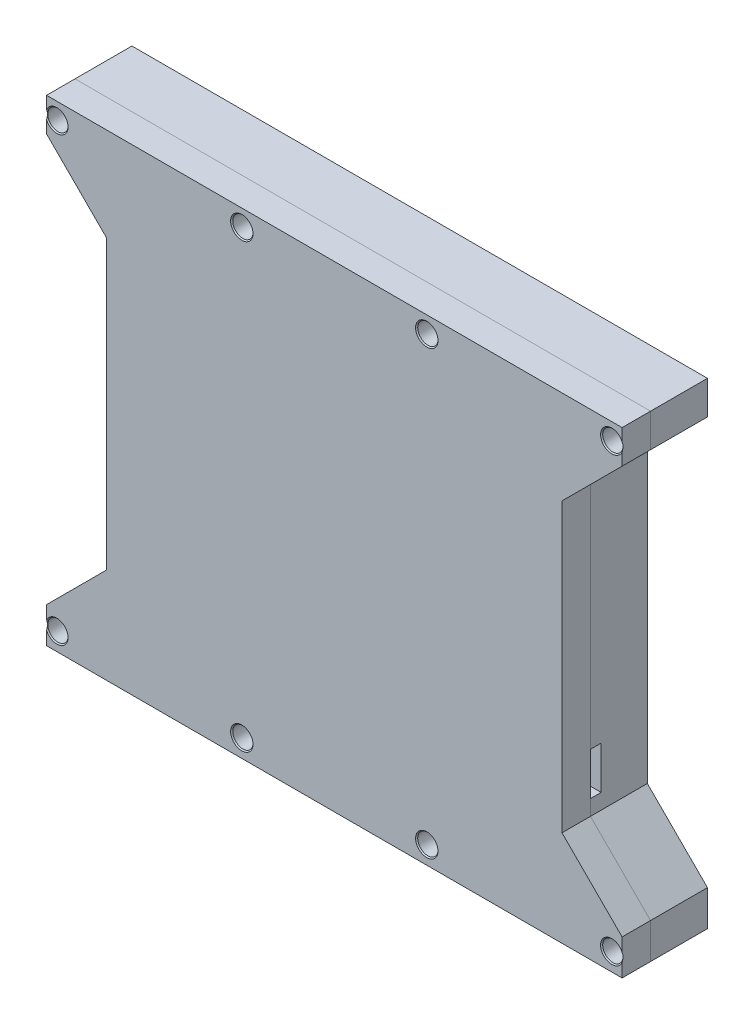
SolidWorks part; units mm, degrees
ref_plane "Front Plane" through (0, 0, 0) normal (0, 0, 1) x (1, 0, 0)
ref_plane "Top Plane" through (0, 0, 0) normal (0, 1, 0) x (1, 0, 0)
ref_plane "Right Plane" through (0, 0, 0) normal (1, 0, 0) x (0, 0, -1)
sketch "Sketch1" plane through (0, 0, 0) normal (0, 0, 1) x (1, 0, 0)
  line L9 (98.5, 67.7634) -> (0, 67.7634) construction
  line L10 (-90.3, -66.2366) -> (0, -66.2366) construction
  line L11 (-80.9, 58.3634) -> (-64, 41.4634)
  line L12 (-64, 41.4634) -> (-64, -39.3366)
  line L13 (-64, -39.3366) -> (-80.9, -56.2366)
  line L18 (-80.9, 67.7634) -> (-80.9, 61.3891) construction
  line L19 (0, -30.5366) -> (0, -67.9366) construction
  line L20 (-80.9, 58.3634) -> (-80.9, 67.7634)
  line L22 (-80.9, -56.2366) -> (-80.9, 58.3634) construction
  line L23 (-80.9, -66.2366) -> (80.9, -66.2366)
  line L25 (-80.9, -66.2366) -> (-80.9, -56.2366)
  line L26 (-80.9, 67.7634) -> (80.9, 67.7634)
  line L27 (80.9, -66.2366) -> (80.9, -56.2366)
  line L28 (0, 58.3634) -> (0, -66.2366) construction
  line L29 (252.3, -56.2366) -> (71.7, -56.2366) construction
  line L30 (-60, -56.2366) -> (60, -56.2366)
  line L31 (-60, -56.2366) -> (-60, 58.3634)
  line L32 (-60, 58.3634) -> (60, 58.3634)
  line L33 (60, -56.2366) -> (60, 58.3634)
  line L34 (69.2, 58.3634) -> (254.8, 58.3634) construction
  line L35 (80.9, -66.2366) -> (80.9, -56.2366)
  line L36 (64, -39.3366) -> (80.9, -56.2366)
  line L37 (64, 41.4634) -> (64, -39.3366)
  line L38 (80.9, 58.3634) -> (64, 41.4634)
  line L39 (80.9, 58.3634) -> (80.9, 67.7634)
  line L40 (80.9, 58.3634) -> (80.9, 67.7634)
  line L41 (80.9, -56.2366) -> (80.9, 58.3634) construction
  line L42 (-92.8, 58.3634) -> (0, 58.3634) construction
  point P37 (0, 67.7634)
  dimension "D1" = 45
  dimension "D2" = 4
  dimension "D3" = 120
  dimension "D4" = 45
  dimension "D5" = 4
extrude "Boss-Extrude1" add sketch "Sketch1" along normal blind 0.8 contours L23 L27 L26 L25 L33 L30 L31 L32 | L30 L33 L32 L31 region at (-78.7992, 63.0634, 0) region at (0, 1.0634, 0)
extrude "Boss-Extrude2" add sketch "Sketch1<3>" along normal blind 24 contours L26 L25 region at (-78.7992, 63.0634, 0)
sketch "Sketch1<3>" plane through (0, 0, 0) normal (0, 0, 1) x (1, 0, 0) same geometry as "Sketch1"
extrude "Boss-Extrude3" add sketch "Sketch1<4>" against normal blind 0.8 from surface contours L38 L39 L26 L20 L11 L12 L13 L25 L23 L27 L36 L37 L33 L30 L31 L32 | L30 L33 L32 L31 region at (-78.7992, 63.0634, 0) region at (0, 1.0634, 0) starting at face at (0, 1.0634, 24)
sketch "Sketch1<4>" plane through (0, 0, 0) normal (0, 0, 1) x (1, 0, 0) same geometry as "Sketch1"
sketch "Sketch2" plane through (0, 0, 0) normal (0, 0, -1) x (-1, 0, 0)
  circle A0 centre (78, -61.2366) radius 1.75
  circle A1 centre (26, -61.2366) radius 1.75
  circle A2 centre (-26, -61.2366) radius 1.75
  circle A3 centre (-78, -61.2366) radius 1.75
  circle A4 centre (78, 63.0634) radius 1.75
  circle A5 centre (26, 63.0634) radius 1.75
  circle A6 centre (-26, 63.0634) radius 1.75
  circle A7 centre (-78, 63.0634) radius 1.75
  circle A8 centre (78, 63.0634) radius 1.75 construction
  circle A9 centre (26, 63.0634) radius 1.75 construction
  circle A10 centre (-26, 63.0634) radius 1.75 construction
  dimension "D1" = 3.5
extrude "Cut-Extrude1" cut sketch "Sketch2" against normal through all
sketch "Sketch3" plane through (0, 0, 24) normal (0, 0, 1) x (1, 0, 0)
  circle A0 centre (-78, -61.2366) radius 2.85
  circle A1 centre (-26, -61.2366) radius 2.85
  circle A2 centre (26, -61.2366) radius 2.85
  circle A3 centre (78, -61.2366) radius 2.85
  circle A4 centre (78, 63.0634) radius 2.85
  circle A5 centre (26, 63.0634) radius 2.85
  circle A6 centre (-26, 63.0634) radius 2.85
  circle A7 centre (-78, 63.0634) radius 2.85
  dimension "D1" = 5.7
extrude "Cut-Extrude2" cut sketch "Sketch3" against normal blind 5.8
ref_plane "Plane1" through (0, 0, 16) normal (0, 0, 1) x (1, 0, 0)
sketch "Sketch4" plane through (0, 0, 0.8) normal (0, 0, 1) x (1, 0, 0)
  line L1 (-50, -46) -> (22, -46)
  line L2 (-50, -46) -> (-50, 46)
  line L3 (-50, 46) -> (22, 46)
  line L4 (22, -46) -> (22, 46)
  line L5 (-60, 58.3634) -> (-60, -56.2366) construction
  line L6 (32, 46) -> (56, 46)
  line L7 (32, 46) -> (32, -8)
  line L8 (32, -8) -> (56, -8)
  line L9 (56, 46) -> (56, -8)
  line L15 (-39, -20.9366) -> (-49, -20.9366) construction
  line L16 (-39, -25.9366) -> (-49, -25.9366)
  line L17 (-39, -15.9366) -> (-49, -15.9366)
  line L18 (-100, -48.9366) -> (-100, 51.0634) construction
  line L19 (-93, -55.9366) -> (93, -55.9366) construction
  circle A0 centre (-44.92, 40.41) radius 1.6
  circle A1 centre (16.03, 40.41) radius 1.6
  circle A2 centre (16.03, -40.92) radius 1.6
  circle A3 centre (-44.92, -40.92) radius 1.6
  circle A4 centre (53.5, 37) radius 1.5
  circle A5 centre (34.8, 2.3) radius 1.5
  arc A6 (-39, -25.9366) -> (-39, -15.9366) centre (-39, -20.9366) ccw
  arc A7 (-49, -15.9366) -> (-49, -25.9366) centre (-49, -20.9366) ccw
  point P21 (22, 0)
  point P30 (-44, -20.9366)
  point P40 (-34, -20.9366)
  dimension "D3" = 3.2
  dimension "D12" = 3
  dimension "D22" = 20
  dimension "D19" = 5
  dimension "D1" = 72
  dimension "D2" = 92
  dimension "D4" = 5.08
  dimension "D5" = 5.59
  dimension "D6" = 5.08
  dimension "D7" = 10
  dimension "D8" = 5.97
  dimension "D9" = 24
  dimension "D10" = 54
  dimension "D11" = 10
  dimension "D13" = 7.5
  dimension "D14" = 1
  dimension "D15" = 8.8
  dimension "D16" = 1.3
  dimension "D17" = 56
  dimension "D18" = 35
sketch "Sketch6" plane through (0, 0, 0.8) normal (0, 0, 1) x (1, 0, 0)
  line L0 (-50, -46) -> (-50, 46) construction
  line L1 (-42.17, 38.8223) -> (-42.17, 41.9977)
  line L2 (-42.17, 41.9977) -> (-44.92, 43.5854)
  line L3 (-44.92, 43.5854) -> (-47.67, 41.9977)
  line L4 (-47.67, 41.9977) -> (-47.67, 38.8223)
  line L5 (-47.67, 38.8223) -> (-44.92, 37.2346)
  line L6 (-44.92, 37.2346) -> (-42.17, 38.8223)
  line L8 (18.78, 38.8223) -> (18.78, 41.9977)
  line L9 (18.78, 41.9977) -> (16.03, 43.5854)
  line L10 (16.03, 43.5854) -> (13.28, 41.9977)
  line L11 (13.28, 41.9977) -> (13.28, 38.8223)
  line L12 (13.28, 38.8223) -> (16.03, 37.2346)
  line L13 (16.03, 37.2346) -> (18.78, 38.8223)
  line L14 (18.78, -42.5077) -> (18.78, -39.3323)
  line L15 (18.78, -39.3323) -> (16.03, -37.7446)
  line L16 (16.03, -37.7446) -> (13.28, -39.3323)
  line L17 (13.28, -39.3323) -> (13.28, -42.5077)
  line L18 (13.28, -42.5077) -> (16.03, -44.0954)
  line L19 (16.03, -44.0954) -> (18.78, -42.5077)
  line L20 (-42.17, -39.3323) -> (-44.92, -37.7446)
  line L21 (-44.92, -37.7446) -> (-47.67, -39.3323)
  line L22 (-47.67, -39.3323) -> (-47.67, -42.5077)
  line L23 (-47.67, -42.5077) -> (-44.92, -44.0954)
  line L24 (-44.92, -44.0954) -> (-42.17, -42.5077)
  line L25 (-42.17, -42.5077) -> (-42.17, -39.3323)
  circle A0 centre (-44.92, 40.41) radius 2.75 construction
  circle A1 centre (-44.92, 40.41) radius 3.95
  circle A2 centre (16.03, 40.41) radius 2.75 construction
  circle A3 centre (16.03, -40.92) radius 2.75 construction
  circle A4 centre (-44.92, -40.92) radius 2.75 construction
  circle A5 centre (-44.92, -40.92) radius 3.95
  circle A6 centre (16.03, -40.92) radius 3.95
  circle A7 centre (16.03, 40.41) radius 3.95
  dimension "D1" = 5.5
  dimension "D2" = 1.2
extrude "Boss-Extrude4" add sketch "Sketch6" along normal blind 4.5
extrude "Boss-Extrude5" add sketch "Sketch6<3>" along normal blind 0.5 contours L5 L6 L1 L2 L3 L4 | L12 L13 L8 L9 L10 L11 | L18 L19 L14 L15 L16 L17 | L24 L25 L20 L21 L22 L23 region at (-44.92, 40.41, 0.8) region at (16.03, 40.41, 0.8) region at (16.03, -40.92, 0.8) region at (-44.92, -40.92, 0.8)
sketch "Sketch6<3>" plane through (0, 0, 0.8) normal (0, 0, 1) x (1, 0, 0) same geometry as "Sketch6"
sketch "Sketch7" plane through (0, 0, 0.8) normal (0, 0, 1) x (1, 0, 0)
  line L0 (16.03, 43.5854) -> (13.28, 41.9977) construction
  line L1 (55.0877, 39.75) -> (51.9123, 39.75)
  line L2 (51.9123, 39.75) -> (50.3246, 37)
  line L3 (50.3246, 37) -> (51.9123, 34.25)
  line L4 (51.9123, 34.25) -> (55.0877, 34.25)
  line L5 (55.0877, 34.25) -> (56.6754, 37)
  line L6 (56.6754, 37) -> (55.0877, 39.75)
  line L7 (36.3877, 5.05) -> (33.2123, 5.05)
  line L8 (33.2123, 5.05) -> (31.6246, 2.3)
  line L9 (31.6246, 2.3) -> (33.2123, -0.45)
  line L10 (33.2123, -0.45) -> (36.3877, -0.45)
  line L11 (36.3877, -0.45) -> (37.9754, 2.3)
  line L12 (37.9754, 2.3) -> (36.3877, 5.05)
  circle A0 centre (53.5, 37) radius 2.75 construction
  circle A1 centre (34.8, 2.3) radius 2.75 construction
  circle A2 centre (34.8, 2.3) radius 3.95
  circle A3 centre (53.5, 37) radius 3.95
  circle A4 centre (16.03, 40.41) radius 3.95 construction
extrude "Boss-Extrude6" add sketch "Sketch7" along normal blind 2.5
sketch "Sketch8" plane through (-80.9, 0, 0) normal (-1, 0, 0) x (0, 0, 1)
  line L0 (16, -73.7) -> (16, 73.7) construction
  circle A0 centre (16, 0) radius 2.5
  dimension "D1" = 5
extrude "Cut-Extrude3" cut sketch "Sketch8" against normal up to surface (20.9 mm away) contours A0 up to face at (-60, 1.0634, 12)
extrude "Cut-Extrude4" cut sketch "Sketch4" against normal through all contours L17 A7 L2 L16 A6 | L2 A7 region at (-51.6718, -20.9366, 0.8) region at (-42.4915, -20.9366, 0.8)
split "Split1" trim tools "Plane1" bodies to split 111 resulting bodies 122 123
sketch "Sketch13" plane through (64, 0, 0) normal (1, 0, 0) x (0, 0, -1)
  line L5 (-16, 73.7) -> (-16, -73.7) construction
  line L6 (-16, -35) -> (-13, -35)
  line L7 (-16, -35) -> (-16, -23)
  line L8 (-16, -23) -> (-13, -23)
  line L9 (-13, -35) -> (-13, -23)
  line L10 (-16, 41.4634) -> (-16, -39.3366) construction
  dimension "D1" = 3
  dimension "D2" = 12
  dimension "D3" = 15
extrude "Cut-Extrude8" cut sketch "Sketch13" against normal up to surface (4 mm away) up to face at (60, 1.0634, 8.4)
fillet "Fillet1" radius 0.3 8 edges at (-75.15, -61.2366, 24) (-23.15, -61.2366, 24) (28.85, -61.2366, 24) (80.85, -61.2366, 24) (80.85, 63.0634, 24) (28.85, 63.0634, 24) (-23.15, 63.0634, 24) (-75.15, 63.0634, 24) profile chamfer
chamfer "Chamfer1" distance 0.3 angle 45 8 edges at (-79.75, 63.0634, 0) (-79.75, -61.2366, 0) (-27.75, -61.2366, 0) (24.25, -61.2366, 0) (76.25, -61.2366, 0) (76.25, 63.0634, 0) (24.25, 63.0634, 0) (-27.75, 63.0634, 0)
